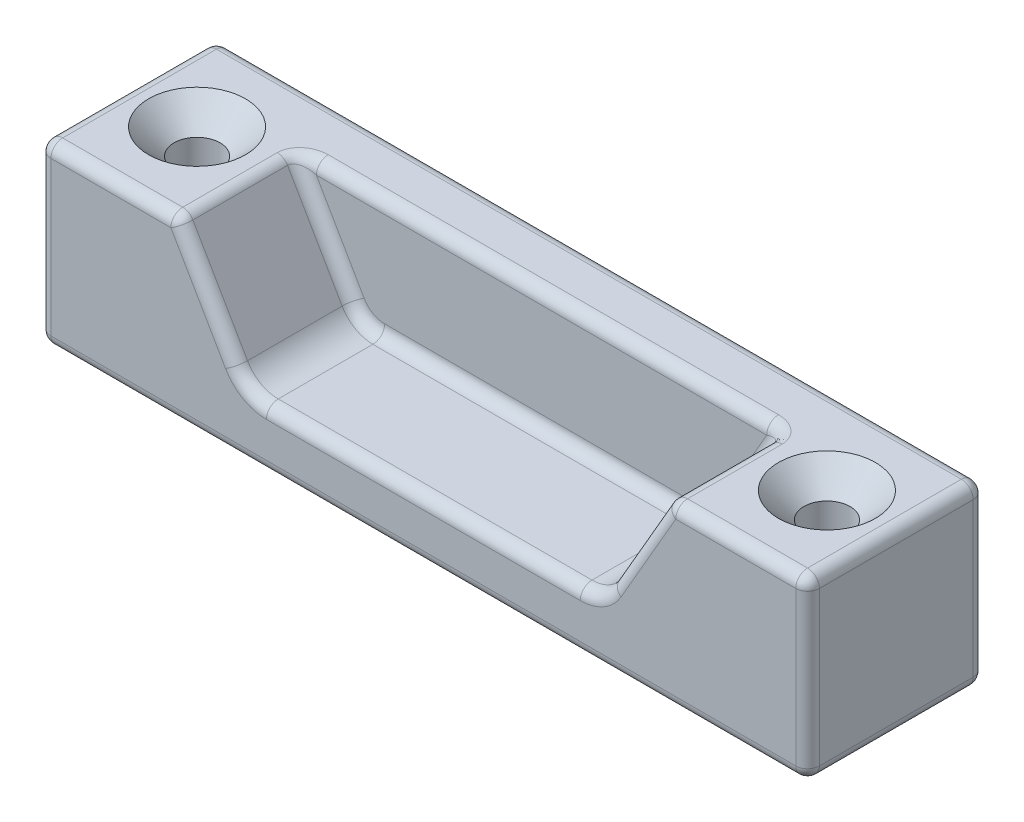
SolidWorks part; units mm, degrees
ref_plane "Płaszczyzna przednia" through (0, 0, 0) normal (0, 0, 1) x (1, 0, 0)
ref_plane "Płaszczyzna górna" through (0, 0, 0) normal (0, 1, 0) x (1, 0, 0)
ref_plane "Płaszczyzna prawa" through (0, 0, 0) normal (1, 0, 0) x (0, 0, -1)
sketch "Szkic1" plane through (0, 0, 0) normal (0, 0, 1) x (1, 0, 0)
  line L1 (-32.5, 15) -> (32.5, 15)
  line L2 (-32.5, 15) -> (-32.5, 0)
  line L3 (-32.5, 0) -> (32.5, 0)
  line L4 (32.5, 15) -> (32.5, 0)
  line L5 (-32.5, 15) -> (32.5, 0) construction
  line L6 (-32.5, 0) -> (32.5, 15) construction
  point P0 (0, 7.5)
  point P5 (0, 0)
  dimension "D1" = 65
  dimension "D2" = 15
extrude "Dodanie-wyciągnięcie1" add sketch "Szkic1" along normal blind 5
sketch "Szkic2" plane through (0, 0, 5) normal (0, 0, 1) x (1, 0, 0)
  line L0 (-20.7735, 15) -> (-15, 5)
  line L1 (-15, 5) -> (15, 5)
  line L2 (15, 5) -> (20.7735, 15)
  line L3 (0, 0) -> (0, -7.4026) construction
  line L4 (32.5, 0) -> (32.5, 15)
  line L5 (32.5, 15) -> (-32.5, 15)
  line L6 (-32.5, 15) -> (-32.5, 0)
  line L7 (-32.5, 0) -> (32.5, 0)
  line L8 (32.5, 0) -> (32.5, 15)
  line L9 (32.5, 15) -> (20.7735, 15)
  line L10 (-32.5, 15) -> (-32.5, 0)
  line L11 (-32.5, 0) -> (32.5, 0)
  line L12 (-20.7735, 15) -> (-32.5, 15)
  point P11 (0, 5)
  dimension "D1" = 0
  dimension "D2" = 120
  dimension "D3" = 30
  dimension "D4" = 5
extrude "Dodanie-wyciągnięcie2" add sketch "Szkic2" along normal blind 10
fillet "Zaokrąglenie1" radius 3 2 edges at (15, 5, 10) (-15, 5, 10)
hole_wizard "Pogłębienie stożkowe pod M3.5 wkręt do części metalowych z łbem soczewkowym1" positions "Szkic4" profile "Szkic5" countersink size "M3.5" standard "Ansi Metric" end condition through all
sketch "Szkic4" plane through (0, 15, 0) normal (0, 1, 0) x (1, 0, 0)
  line L0 (-32.5, -15) -> (-32.5, 0) construction
  line L1 (32.5, -15) -> (20.7735, -15) construction
  line L2 (-20.7735, -15) -> (-32.5, -15) construction
  point P0 (-26.6368, -7.5)
  point P2 (26.6368, -7.5)
  point P6 (-32.5, -7.5)
  point P9 (26.6368, -15)
  point P12 (-26.6368, -15)
sketch "Szkic5" plane through (-26.6368, 15, 7.5) normal (1, 0, 0) x (0, 0, 1)
  line L0 (0, 0) -> (0, 15)
  line L1 (0, 15) -> (1.95, 15)
  line L2 (1.95, 15) -> (1.95, 2.15)
  line L3 (1.95, 2.15) -> (4.1, 0)
  line L5 (4.1, 0) -> (0, 0)
  line L6 (-1.95, 2.15) -> (-4.1, 0) construction
  line L11 (0, -6.35) -> (0, 107.95) construction
  dimension "Średnica otworu na wylot" = 3.9
  dimension "Głębokość otworu na wylot" = 15
  dimension "Średnica zewnętrznego pogłębienia stożkowego" = 8.2
  dimension "Kąt zewnętrznego pogłębienia stożkowego" = 90
fillet "Zaokrąglenie2" radius 1 26 edges at (-14.7679, 5.4019, 5) (0, 5, 5) (-14.7679, 5.4019, 15) (0, 5, 15) (-18.3198, 10.75, 5) (14.7679, 5.4019, 5) (-20.7735, 15, 10) (-18.3198, 10.75, 15) (14.7679, 5.4019, 15) (0, 15, 5) (18.3198, 10.75, 5) (-26.6368, 15, 15) (-32.5, 15, 7.5) (-32.5, 7.5, 0) (18.3198, 10.75, 15) (20.7735, 15, 10) (0, 15, 0) (-32.5, 7.5, 15) (-32.5, 0, 7.5) (32.5, 7.5, 0) (0, 0, 0) (26.6368, 15, 15) (32.5, 15, 7.5) (0, 0, 15) (32.5, 0, 7.5) (32.5, 7.5, 15)
